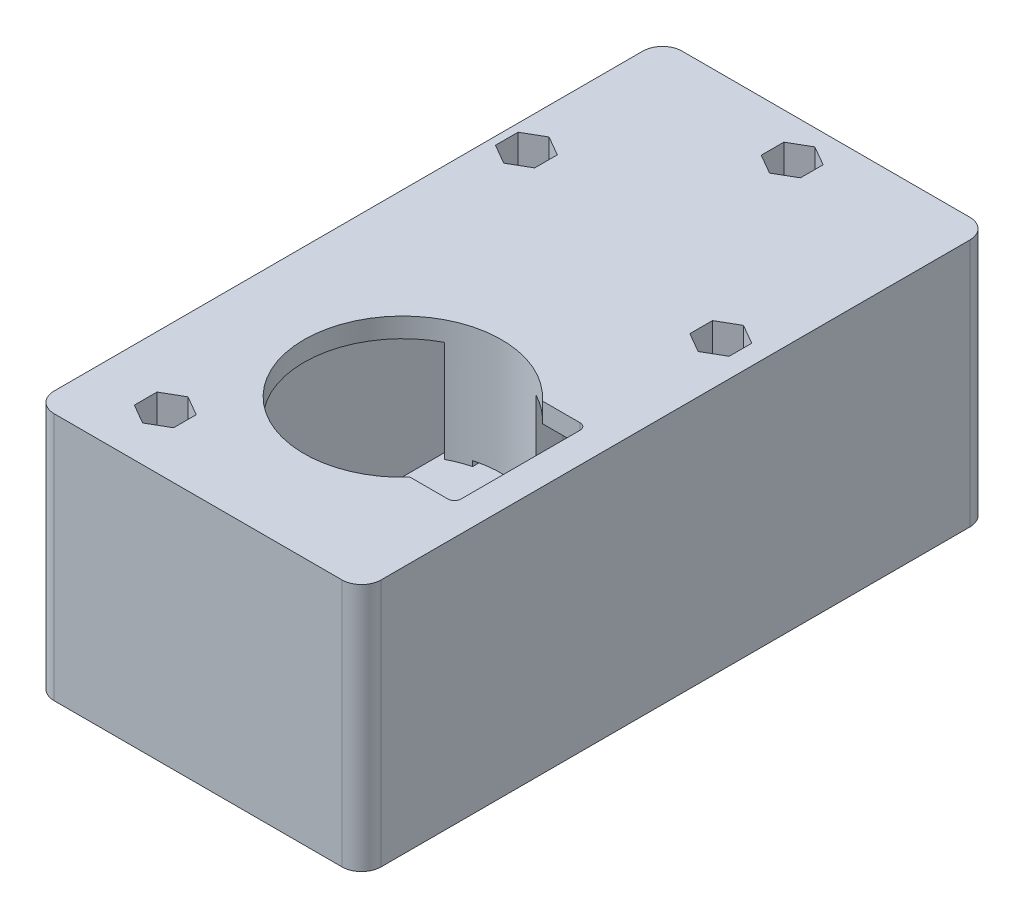
SolidWorks part; units mm, degrees
ref_plane "前视基准面" through (0, 0, 0) normal (0, 0, 1) x (1, 0, 0)
ref_plane "上视基准面" through (0, 0, 0) normal (0, 1, 0) x (1, 0, 0)
ref_plane "右视基准面" through (0, 0, 0) normal (1, 0, 0) x (0, 0, -1)
sketch "草图1" plane through (0, 0, 0) normal (0, 0, 1) x (1, 0, 0)
  line L1 (50, 38) -> (0, 38)
  line L2 (50, 38) -> (50, 0)
  line L3 (50, 0) -> (0, 0)
  line L4 (0, 38) -> (0, 0)
  dimension "D1" = 50
  dimension "D2" = 38
extrude "凸台-拉伸1" add sketch "草图1" against normal blind 3
sketch "草图2" plane through (0, 0, 0) normal (0, 0, 1) x (1, 0, 0)
  line L8 (50, 0) -> (50, 38)
  line L9 (50, 38) -> (0, 38)
  line L10 (0, 38) -> (0, 0)
  line L11 (0, 0) -> (50, 0)
  line L12 (50, 0) -> (50, 38)
  line L13 (50, 38) -> (0, 38)
  line L14 (0, 38) -> (0, 0)
  line L15 (0, 0) -> (50, 0)
  line L20 (47, 3) -> (47, 35)
  line L21 (47, 35) -> (3, 35)
  line L22 (3, 35) -> (3, 3)
  line L23 (3, 3) -> (47, 3)
  line L24 (47, 3) -> (47, 35)
  line L25 (47, 35) -> (3, 35)
  line L26 (3, 35) -> (3, 3)
  line L27 (3, 3) -> (47, 3)
  dimension "D1" = 0
  dimension "D2" = 3
extrude "凸台-拉伸2" add sketch "草图2" along normal blind 90
sketch "草图4" plane through (0, 0, -3) normal (0, 0, -1) x (-1, 0, 0)
  line L0 (-50, 38) -> (0, 38) construction
  line L1 (0, 38) -> (0, 0) construction
  circle A0 centre (-12.5, 10.5) radius 7.3
  dimension "D1" = 14.6
  dimension "D3" = 12.5
  dimension "D2" = 27.5
extrude "切除-拉伸1" cut sketch "草图4" against normal blind 45.2
sketch "草图5" plane through (0, 0, 0) normal (0, 0, 1) x (1, 0, 0)
  circle A0 centre (12.5, 10.5) radius 7.3
  circle A1 centre (12.5, 10.5) radius 7.3 construction
  circle A2 centre (12.5, 10.5) radius 10.3
  dimension "D1" = 3
extrude "凸台-拉伸3" add sketch "草图5" along normal blind 16
sketch "草图6" plane through (0, 0, -3) normal (0, 0, -1) x (-1, 0, 0)
  circle A0 centre (-12.5, 10.5) radius 5.8
  circle A3 centre (-12.5, 10.5) radius 7.3 construction
  circle A4 centre (-12.5, 10.5) radius 8.3
  circle A5 centre (-12.5, 10.5) radius 8.3
  dimension "D1" = 1
  dimension "D2" = 1.5
extrude "凸台-拉伸5" add sketch "草图6" against normal blind 1
sketch "草图7" plane through (0, 0, 16) normal (0, 0, 1) x (1, 0, 0)
  line L2 (5.4403, 3) -> (19.5597, 3)
  line L4 (5.4403, 3) -> (19.5597, 3)
  line L5 (3, 14.4799) -> (3, 6.5201)
  line L8 (3, 14.4799) -> (3, 6.5201)
  arc A1 (3, 6.5201) -> (5.4403, 3) centre (12.5, 10.5) ccw
  arc A2 (3, 6.5201) -> (5.4403, 3) centre (12.5, 10.5) ccw
  circle A3 centre (12.5, 10.5) radius 4.3
  arc A10 (19.5597, 3) -> (3, 14.4799) centre (12.5, 10.5) ccw
  arc A11 (19.5597, 3) -> (3, 14.4799) centre (12.5, 10.5) ccw
  dimension "D2" = 8.6
  dimension "D1" = 0
extrude "凸台-拉伸6" add sketch "草图7" along normal blind 2
sketch "草图8" plane through (0, 0, 18) normal (0, 0, 1) x (1, 0, 0)
  circle A1 centre (12.5, 10.5) radius 6.3
  circle A2 centre (12.5, 10.5) radius 4.3
  circle A3 centre (12.5, 10.5) radius 4.3
  dimension "D1" = 0
  dimension "D2" = 2
extrude "凸台-拉伸7" add sketch "草图8" along normal blind 10
sketch "草图9" plane through (0, 0, 28) normal (0, 0, 1) x (1, 0, 0)
  line L0 (8.2, 10.5) -> (16.8, 10.5) construction
  line L2 (16.1644, 8.25) -> (18.8, 8.25)
  line L3 (16.1644, 8.25) -> (16.1644, 12.75)
  line L4 (16.1644, 12.75) -> (18.8, 12.75)
  line L5 (18.8, 8.25) -> (18.8, 12.75)
  circle A0 centre (12.5, 10.5) radius 4.3 construction
  circle A1 centre (12.5, 10.5) radius 6.3 construction
  dimension "D1" = 4.5
extrude "切除-拉伸2" cut sketch "草图9" against normal blind 4
sketch "草图10" plane through (0, 3, 0) normal (0, 1, 0) x (1, 0, 0)
  line L0 (19.33, -36.76) -> (19.33, -34.76)
  line L1 (19.33, -34.76) -> (22.03, -34.76)
  line L2 (22.03, -34.76) -> (22.03, -36.76)
  line L3 (22.03, -36.76) -> (19.33, -36.76)
  line L8 (23.23, -37.46) -> (23.23, -28) construction
  line L9 (23.43, -37.46) -> (23.03, -37.46) construction
  line L10 (16.8, -28) -> (29.66, -28) construction
  line L11 (27.13, -34.76) -> (24.43, -34.76)
  line L12 (24.43, -34.76) -> (24.43, -36.76)
  line L13 (24.43, -36.76) -> (27.13, -36.76)
  line L14 (27.13, -36.76) -> (27.13, -34.76)
  line L15 (18.53, -37.26) -> (18.53, -34.14) construction
  line L16 (22.83, -37.26) -> (22.83, -34.14) construction
  line L17 (20.92, -34.36) -> (18.92, -34.36) construction
  circle A0 centre (19.92, -32.88) radius 0.7
  circle A1 centre (26.54, -32.88) radius 0.7
  circle A2 centre (19.92, -32.88) radius 0.98 construction
  point P14 (18.53, -35.7)
  dimension "D1" = 1.4
  dimension "D2" = 0.28
  dimension "D3" = 0.8
  dimension "D4" = 0.8
  dimension "D5" = 0.4
  dimension "D6" = 2
extrude "凸台-拉伸8" add sketch "草图10" along normal blind 32
sketch "草图11" plane through (0, 3, 0) normal (0, 1, 0) x (1, 0, 0)
  line L0 (16.8, -34.14) -> (16.8, -28) construction
  line L1 (16.2, -36.76) -> (30.26, -36.76)
  line L2 (16.2, -36.76) -> (16.2, -27.4)
  line L3 (16.2, -27.4) -> (30.26, -27.4)
  line L4 (30.26, -36.76) -> (30.26, -27.4)
  line L5 (29.66, -28) -> (29.66, -34.14) construction
  line L6 (19.33, -36.76) -> (22.03, -36.76) construction
  line L7 (16.8, -28) -> (29.66, -28) construction
  dimension "D1" = 0.6
  dimension "D2" = 0.6
  dimension "D3" = 0.6
extrude "凸台-拉伸9" add sketch "草图11" along normal blind 4.4
sketch "草图12" plane through (0, 35, 0) normal (0, -1, 0) x (1, 0, 0)
  line L1 (16.2, 27.4) -> (30.26, 27.4)
  line L2 (16.2, 27.4) -> (16.2, 36.76)
  line L3 (16.2, 36.76) -> (30.26, 36.76)
  line L4 (30.26, 27.4) -> (30.26, 36.76)
extrude "凸台-拉伸10" add sketch "草图12" along normal blind 21.2
sketch "草图13" plane through (0, 38, 0) normal (0, 1, 0) x (1, 0, 0)
  line L0 (12.3, -64.096) -> (42.5, -64.096) construction
  line L1 (40.04, -72.896) -> (39.0237, -72.896) construction
  line L2 (38.625, -74.196) -> (44.4, -74.196)
  line L3 (45.4, -73.196) -> (45.4, -54.996)
  line L4 (44.4, -57.796) -> (44.4, -70.396) construction
  line L5 (38.625, -53.996) -> (44.4, -53.996)
  circle A0 centre (27.4, -64.096) radius 15.1 construction
  circle A1 centre (27.4, -64.096) radius 14.1 construction
  arc A2 (38.625, -74.196) -> (38.625, -53.996) centre (27.4, -64.096) cw
  arc A3 (44.4, -53.996) -> (45.4, -54.996) centre (44.4, -54.996) cw
  arc A4 (44.4, -74.196) -> (45.4, -73.196) centre (44.4, -73.196) ccw
  point P16 (45.4, -64.096)
  point P18 (45.4, -53.996)
  point P21 (45.4, -74.196)
  dimension "D1" = 1
  dimension "D2" = 1.3
  dimension "D4" = 1
  dimension "D3" = 1
extrude "切除-拉伸3" cut sketch "草图13" against normal blind 3
sketch "草图14" plane through (0, 35, 0) normal (0, -1, 0) x (1, 0, 0)
  line L0 (14.3, 64.096) -> (40.5, 64.096) construction
  line L1 (23.9, 46.596) -> (23.9, 50.4373) construction
  line L2 (30.9, 46.596) -> (30.9, 50.4373) construction
  line L3 (23.9, 46.596) -> (23.9, 49.4072)
  line L4 (30.9, 46.596) -> (30.9, 49.4072)
  line L5 (30.9, 81.596) -> (30.9, 78.7847)
  line L6 (23.9, 81.596) -> (23.9, 78.7847)
  circle A0 centre (27.4, 46.596) radius 1.65
  circle A1 centre (27.4, 64.096) radius 13.1 construction
  arc A2 (23.9, 49.4072) -> (30.9, 49.4072) centre (27.4, 64.096) ccw
  arc A3 (38.625, 74.196) -> (38.625, 53.996) centre (27.4, 64.096) ccw construction
  arc A4 (23.9, 46.596) -> (30.9, 46.596) centre (27.4, 46.596) ccw
  arc A5 (23.9, 46.596) -> (30.9, 46.596) centre (27.4, 46.596) ccw construction
  arc A6 (23.9, 81.596) -> (30.9, 81.596) centre (27.4, 81.596) cw
  arc A7 (23.9, 78.7847) -> (30.9, 78.7847) centre (27.4, 64.096) cw
  circle A8 centre (27.4, 81.596) radius 1.65
  dimension "D1" = 3.3
extrude "凸台-拉伸11" add sketch "草图14" along normal blind 15.5
sketch "草图15" plane through (0, 35, 0) normal (0, -1, 0) x (1, 0, 0)
  line L0 (23.9, 46.596) -> (23.9, 50.4373) construction
  line L1 (20.4, 50.7165) -> (20.4, 46.596)
  line L2 (27.4, 48.696) -> (27.4, 44.496) construction
  line L4 (34.4, 50.7165) -> (34.4, 46.596)
  line L5 (45.4, 64.096) -> (12.3, 64.096) construction
  line L6 (45.4, 73.196) -> (45.4, 54.996) construction
  line L7 (20.4, 77.4754) -> (20.4, 81.596)
  line L8 (34.4, 77.4754) -> (34.4, 81.596)
  circle A0 centre (27.4, 46.596) radius 1.65
  circle A1 centre (27.4, 46.596) radius 2.1 construction
  arc A2 (20.4, 46.596) -> (34.4, 46.596) centre (27.4, 46.596) ccw
  arc A3 (20.4, 50.7165) -> (34.4, 50.7165) centre (27.4, 64.096) ccw
  arc A4 (23.9, 78.7847) -> (23.9, 49.4072) centre (27.4, 64.096) ccw construction
  arc A5 (20.4, 77.4754) -> (34.4, 77.4754) centre (27.4, 64.096) cw
  circle A6 centre (27.4, 81.596) radius 1.65
  arc A7 (20.4, 81.596) -> (34.4, 81.596) centre (27.4, 81.596) cw
  arc A9 (30.9, 49.4072) -> (38.625, 53.996) centre (27.4, 64.096) ccw construction
  line M14 (23.9, 78.7847) -> (23.9, 81.596)
  arc M15 (23.9, 81.596) -> (30.9, 81.596) centre (27.4, 81.596) cw
  line M16 (30.9, 81.596) -> (30.9, 78.7847)
  line M24 (30.9, 49.4072) -> (30.9, 46.596)
  arc M25 (30.9, 46.596) -> (23.9, 46.596) centre (27.4, 46.596) cw
  line M26 (23.9, 46.596) -> (23.9, 49.4072)
  dimension "D1" = 3.3
  dimension "D2" = 7
extrude "凸台-拉伸12" add sketch "草图15" along normal blind 15.5 contours L1 A2 L4 M24 M25 M26 | A7 L7 L8 M14 M15 M16 region at (22.0467, 35, 49.7857) region at (20.5788, 35, 79.5357)
sketch "草图16" plane through (0, 19.5, 0) normal (0, -1, 0) x (1, 0, 0)
  line L0 (45.4, 64.096) -> (12.3, 64.096) construction
  line L1 (45.4, 73.196) -> (45.4, 54.996) construction
  line L24 (31.3, 81.596) -> (31.3, 77.2291)
  line L25 (23.5, 77.2291) -> (23.5, 81.596)
  line L26 (31.3, 46.596) -> (31.3, 50.9628)
  line L27 (23.5, 50.9628) -> (23.5, 46.596)
  line L28 (31.3, 46.596) -> (31.3, 50.9628)
  line L29 (23.5, 50.9628) -> (23.5, 46.596)
  arc A0 (20.4, 77.4754) -> (20.4, 50.7165) centre (27.4, 64.096) ccw construction
  arc A25 (23.5, 81.596) -> (31.3, 81.596) centre (27.4, 81.596) cw
  arc A26 (23.5, 77.2291) -> (31.3, 77.2291) centre (27.4, 64.096) cw
  arc A27 (23.5, 50.9628) -> (31.3, 50.9628) centre (27.4, 64.096) ccw
  arc A28 (23.5, 46.596) -> (31.3, 46.596) centre (27.4, 46.596) ccw
  arc A29 (23.5, 50.9628) -> (31.3, 50.9628) centre (27.4, 64.096) ccw
  arc A30 (23.5, 46.596) -> (31.3, 46.596) centre (27.4, 46.596) ccw
  dimension "D1" = 0.4
extrude "切除-拉伸4" cut sketch "草图16" against normal blind 0.8
sketch "草图17" plane through (0, 0, 0) normal (0, 0, 1) x (1, 0, 0)
  line L1 (3, 3) -> (47, 3) construction
  line L2 (22.83, 10.5392) -> (22.83, 3)
  line L3 (22.83, 10.2892) -> (22.83, 10.7892) construction
  line L4 (22.83, 3) -> (19.5597, 3)
  line L5 (5.4403, 3) -> (3, 3)
  line L6 (3, 3) -> (3, 6.5201)
  line L7 (3, 14.4799) -> (3, 35)
  line L8 (3, 35) -> (22.83, 35)
  line L9 (47, 35) -> (3, 35) construction
  line L10 (22.83, 10.5392) -> (22.83, 35)
  arc A1 (5.4403, 3) -> (3, 6.5201) centre (12.5, 10.5) cw
  arc A2 (3, 6.5201) -> (5.4403, 3) centre (12.5, 10.5) ccw construction
  arc A3 (3, 14.4799) -> (19.5597, 3) centre (12.5, 10.5) cw
  arc M1 (3, 14.4799) -> (19.5597, 3) centre (12.5, 10.5) cw
  line M2 (19.5597, 3) -> (47, 3)
  line M4 (47, 35) -> (3, 35)
  line M5 (3, 35) -> (3, 14.4799)
extrude "凸台-拉伸13" add sketch "草图17" along normal blind 18 contours L2 L10 M4 M5 M1 M2 | L5 A1 L6 region at (13.2696, 26.2496, 0) region at (3.7547, 4.0789, 0)
sketch "草图18" plane through (0, 0, 18) normal (0, 0, 1) x (1, 0, 0)
  line L8 (3, 35) -> (3, 3)
  line L9 (3, 3) -> (22.83, 3)
  line L10 (22.83, 3) -> (22.83, 35)
  line L11 (22.83, 35) -> (3, 35)
  line L12 (3, 35) -> (3, 3)
  line L13 (3, 3) -> (22.83, 3)
  line L14 (22.83, 3) -> (22.83, 35)
  line L15 (22.83, 35) -> (3, 35)
  circle A0 centre (12.5, 10.5) radius 6.3
  circle A1 centre (12.5, 10.5) radius 6.3 construction
  dimension "D1" = 0
extrude "凸台-拉伸14" add sketch "草图18" along normal blind 10
sketch "草图19" plane through (0, 0, 28) normal (0, 0, 1) x (1, 0, 0)
  line L0 (18.3845, 8.25) -> (22.83, 8.25)
  line L1 (22.83, 7.4) -> (22.83, 13.8) construction
  line L2 (22.83, 8.25) -> (22.83, 12.75)
  line L3 (22.83, 12.75) -> (18.3845, 12.75)
  line L4 (18.3845, 12.75) -> (16.1644, 12.75) construction
  line L5 (18.3845, 8.25) -> (18.3845, 12.75)
extrude "切除-拉伸5" cut sketch "草图19" against normal blind 4
sketch "草图23" plane through (0, 35, 0) normal (0, -1, 0) x (1, 0, 0)
  line L0 (22.83, 27.4) -> (22.83, 0) construction
  line L1 (22.83, 0) -> (47, 0) construction
  line L2 (22.83, 0) -> (22.83, 9)
  line L3 (22.83, 0) -> (31.83, 0)
  line L4 (47, 90) -> (47, 0) construction
  line L5 (44, 26.08) -> (47, 26.08)
  line L6 (47, 26.08) -> (47, 38.08)
  line L7 (45.65, 32.08) -> (42.35, 32.08) construction
  line L8 (44, 38.08) -> (47, 38.08)
  line L9 (30.26, 32.08) -> (42.35, 32.08) construction
  line L10 (30.26, 36.76) -> (30.26, 27.4) construction
  line L11 (3, 90) -> (3, 28) construction
  line L12 (0, 90) -> (50, 90) construction
  line L13 (11, 82.35) -> (11, 85.65) construction
  line L14 (5, 90) -> (5, 84)
  line L15 (17, 90) -> (17, 84)
  line L16 (5, 90) -> (17, 90)
  circle A0 centre (25.83, 3) radius 1.65
  arc A1 (31.83, 0) -> (22.83, 9) centre (22.83, 0) ccw
  circle A2 centre (44, 32.08) radius 1.65
  arc A3 (44, 26.08) -> (44, 38.08) centre (44, 32.08) cw
  circle A4 centre (11, 84) radius 1.65
  arc A5 (5, 84) -> (17, 84) centre (11, 84) ccw
  point P22 (47, 32.08)
  dimension "D1" = 3
  dimension "D4" = 3.3
  dimension "D5" = 3
  dimension "D6" = 3.3
  dimension "D7" = 6
  dimension "D8" = 3.3
  dimension "D9" = 8
  dimension "D10" = 6
  dimension "D11" = 6
  dimension "D2" = 3
  dimension "D3" = 9
extrude "凸台-拉伸16" add sketch "草图23" along normal through all
sketch "草图25" plane through (0, 35, 0) normal (0, -1, 0) x (1, 0, 0)
  line L0 (0, -3) -> (0, 90) construction
  line L1 (16.2, 28) -> (3, 28) construction
  circle A0 centre (4.2, 22) radius 1.65
  circle A1 centre (4.2, 22) radius 3 construction
  circle A2 centre (25.83, 3) radius 1.65
  circle A7 centre (44, 32.08) radius 1.65
  circle A8 centre (44, 32.08) radius 1.65
  circle A10 centre (11, 84) radius 1.65
  circle A11 centre (11, 84) radius 1.65
  dimension "D1" = 3.3
  dimension "D2" = 6
  dimension "D3" = 4.2
  dimension "D4" = 6
  dimension "D5" = 0
  dimension "D6" = 0
extrude "切除-拉伸7" cut sketch "草图25" against normal through all and the other way through all
sketch "草图26" plane through (0, 38, 0) normal (0, 1, 0) x (1, 0, 0)
  line L0 (0, 3) -> (0, -90) construction
  line L1 (4.2, -18.5371) -> (1.201, -20.2685)
  line L2 (1.201, -20.2685) -> (1.201, -23.7315)
  line L3 (1.201, -23.7315) -> (4.2, -25.4629)
  line L4 (4.2, -25.4629) -> (7.199, -23.7315)
  line L5 (7.199, -23.7315) -> (7.199, -20.2685)
  line L6 (7.199, -20.2685) -> (4.2, -18.5371)
  line L7 (25.83, -6.4629) -> (28.829, -4.7315)
  line L8 (28.829, -4.7315) -> (28.829, -1.2685)
  line L9 (28.829, -1.2685) -> (25.83, 0.4629)
  line L10 (25.83, 0.4629) -> (22.831, -1.2685)
  line L11 (22.831, -1.2685) -> (22.831, -4.7315)
  line L12 (22.831, -4.7315) -> (25.83, -6.4629)
  line L14 (11, -80.5371) -> (8.001, -82.2685)
  line L15 (8.001, -82.2685) -> (8.001, -85.7315)
  line L16 (8.001, -85.7315) -> (11, -87.4629)
  line L17 (11, -87.4629) -> (13.999, -85.7315)
  line L18 (13.999, -85.7315) -> (13.999, -82.2685)
  line L19 (13.999, -82.2685) -> (11, -80.5371)
  line L20 (44, -28.6171) -> (41.001, -30.3485)
  line L21 (41.001, -30.3485) -> (41.001, -33.8115)
  line L22 (41.001, -33.8115) -> (44, -35.5429)
  line L23 (44, -35.5429) -> (46.999, -33.8115)
  line L24 (46.999, -33.8115) -> (46.999, -30.3485)
  line L25 (46.999, -30.3485) -> (44, -28.6171)
  circle A0 centre (4.2, -22) radius 2.999 construction
  circle A1 centre (25.83, -3) radius 2.999 construction
  circle A2 centre (11, -84) radius 2.999 construction
  circle A3 centre (44, -32.08) radius 2.999 construction
  dimension "D1" = 5.998
extrude "切除-拉伸8" cut sketch "草图26" against normal blind 24.5
sketch "草图29" plane through (0, 0, 90) normal (0, 0, 1) x (1, 0, 0)
  line L8 (0, 0) -> (50, 0)
  line L9 (50, 0) -> (50, 38)
  line L10 (50, 38) -> (0, 38)
  line L11 (0, 38) -> (0, 0)
  line L12 (0, 0) -> (50, 0)
  line L13 (50, 0) -> (50, 38)
  line L14 (50, 38) -> (0, 38)
  line L15 (0, 38) -> (0, 0)
  dimension "D1" = 0
extrude "凸台-拉伸17" add sketch "草图29" along normal blind 3
fillet "圆角1" radius 3 4 edges at (50, 19, 93) (50, 19, -3) (0, 19, 93) (0, 19, -3)
